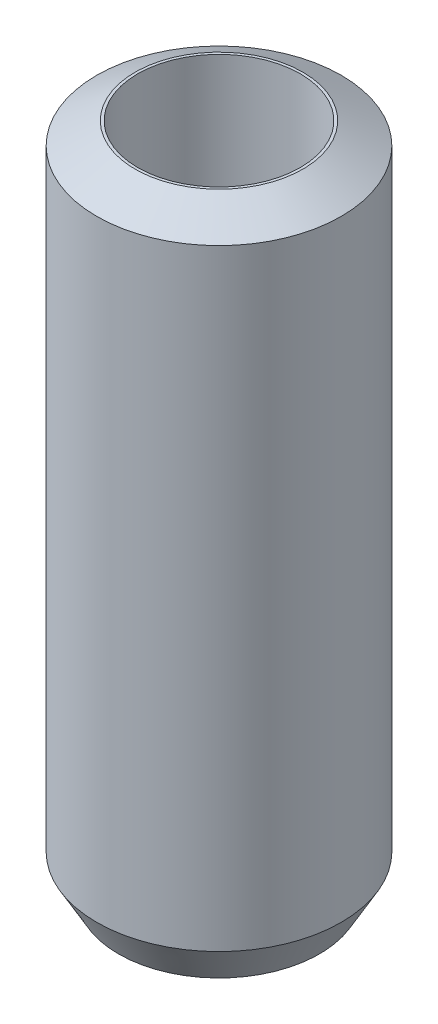
SolidWorks part; units mm, degrees
ref_plane "Front Plane" through (0, 0, 0) normal (0, 0, 1) x (1, 0, 0)
ref_plane "Top Plane" through (0, 0, 0) normal (0, 1, 0) x (1, 0, 0)
ref_plane "Right Plane" through (0, 0, 0) normal (1, 0, 0) x (0, 0, -1)
sketch "Sketch1" plane through (0, 0, 0) normal (0, 1, 0) x (1, 0, 0)
  circle A0 centre (0, 0) radius 10
  dimension "SHAFT_OD" = 20
extrude "Boss-Extrude1" add sketch "Sketch1" along normal blind 54.9265
sketch "Sketch2" plane through (0, 0, 0) normal (0, 1, 0) x (1, 0, 0)
  circle A0 centre (0, 0) radius 6.649
  dimension "BORE_D" = 13.298
extrude "Cut-Extrude1" cut sketch "Sketch2" along normal through all
chamfer "Chamfer1" distance 1.7806 angle 60.374 2 edges at (0, 54.9265, 10) (0, 0, 10) first distance on face at (0, 54.9265, 10) first distance on face at (0, 0, 6.649)
